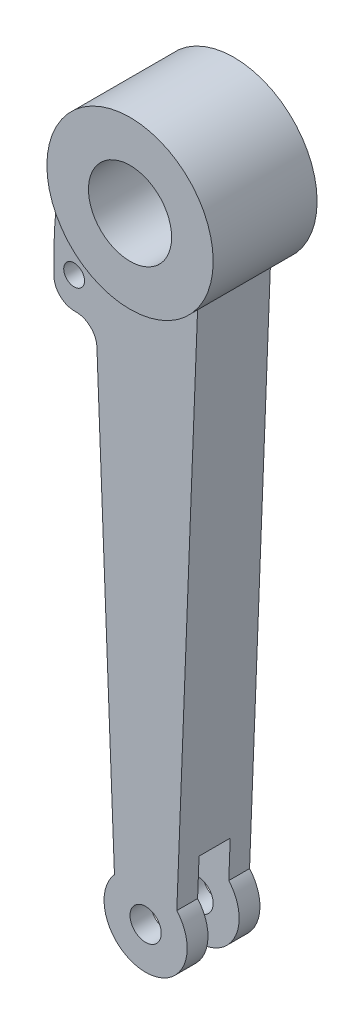
SolidWorks part; units mm, degrees
ref_plane "Front Plane" through (0, 0, 0) normal (0, 0, 1) x (1, 0, 0)
ref_plane "Top Plane" through (0, 0, 0) normal (0, 1, 0) x (1, 0, 0)
ref_plane "Right Plane" through (0, 0, 0) normal (1, 0, 0) x (0, 0, -1)
sketch "Sketch1" plane through (0, 0, 0) normal (0, 0, 1) x (1, 0, 0)
  circle A0 centre (0, 0) radius 40
  circle A1 centre (0, 0) radius 20
  dimension "D1" = 80
  dimension "D2" = 40
extrude "Boss-Extrude1" add sketch "Sketch1" along normal mid plane 50
sketch "Sketch3" plane through (0, 0, 0) normal (0, 0, 1) x (1, 0, 0)
  line L0 (-25, -31.225) -> (-15, -286.7712)
  line L1 (-20, -300) -> (20, -300) construction
  line L2 (15, -286.7712) -> (25, -31.225)
  line L3 (-25, -31.225) -> (0, -31.225) construction
  line L4 (0, -31.225) -> (25, -31.225) construction
  line L5 (0, -31.225) -> (0, 0) construction
  line L6 (-15, -286.7712) -> (15, -286.7712) construction
  circle A0 centre (0, 0) radius 40 construction
  arc A1 (-25, -31.225) -> (25, -31.225) centre (0, 0) ccw
  arc A2 (-15, -286.7712) -> (15, -286.7712) centre (0, -300) ccw
  circle A3 centre (0, -300) radius 7.5
  dimension "D1" = 50
  dimension "D4" = 40
  dimension "D5" = 15
  dimension "D2" = 40
  dimension "D3" = 300
  dimension "D6" = 30
extrude "Boss-Extrude3" add sketch "Sketch3" along normal mid plane 35
sketch "Sketch5" plane through (0, 0, 0) normal (0, 0, 1) x (1, 0, 0)
  circle A0 centre (0, -300) radius 35
  dimension "D1" = 70
extrude "Cut-Extrude1" cut sketch "Sketch5" against normal mid plane 15
sketch "Sketch6" plane through (-26.1818, -1.0245, 0) normal (-0.9992, -0.0391, 0) x (0, 0, 1)
  line L0 (0, 0) -> (0, -267.9024) construction
  line L1 (-7.5, -267.9024) -> (7.5, -267.9024) construction
  line L2 (17.5, -30.2236) -> (17.5, -285.9654) construction
  line L3 (-17.5, -30.2236) -> (17.5, -30.2236)
  line L4 (-17.5, -30.2236) -> (-17.5, -60.2236)
  line L5 (-17.5, -60.2236) -> (17.5, -60.2236)
  line L6 (17.5, -30.2236) -> (17.5, -60.2236)
  line L7 (-17.5, -30.2236) -> (17.5, -60.2236) construction
  line L8 (-17.5, -60.2236) -> (17.5, -30.2236) construction
  line L9 (17.5, -30.2236) -> (-17.5, -30.2236) construction
  line L10 (5, -30.2236) -> (5, -60.2236)
  line L11 (-5, -30.2236) -> (-5, -60.2236)
  line L12 (5, -45.2236) -> (0, -45.2236) construction
  line L13 (0, -45.2236) -> (-5, -45.2236) construction
  point P5 (0, -45.2236)
  line M11 (17.5, -285.9654) -> (17.5, -30.2236)
  line M12 (17.5, -30.2236) -> (-17.5, -30.2236)
  line M13 (-17.5, -30.2236) -> (-17.5, -285.9654)
  dimension "D1" = 30
  dimension "D2" = 10
extrude "Boss-Extrude4" add sketch "Sketch6" along normal blind 20 contours L10 L5 M12 M11 | L11 L5 M12 M13 region at (-24.4135, -46.2135, -11.25) region at (-24.4135, -46.2135, 11.25)
sketch "Sketch7" plane through (0, 0, -17.5) normal (0, 0, -1) x (-1, 0, 0)
  line L0 (44.9847, -32.007) -> (23.8269, -61.202) construction
  circle A0 centre (34.4058, -46.6045) radius 5
  dimension "D1" = 10
extrude "Cut-Extrude2" cut sketch "Sketch7" against normal through all
sketch "Sketch8" plane through (0, 0, -17.5) normal (0, 0, -1) x (-1, 0, 0)
  line L0 (44.9847, -32.007) -> (40, 0)
  line L1 (25, -31.225) -> (44.9847, -32.007)
  line L2 (0, 0) -> (40, 0) construction
  circle A0 centre (0, 0) radius 40 construction
  arc A1 (40, 0) -> (25, -31.225) centre (0, 0) cw
extrude "Boss-Extrude5" add sketch "Sketch8" against normal blind 12.5
mirror "Mirror2" about plane through (0, 0, 0) normal (0, 0, 1) of "Boss-Extrude5"
fillet "Fillet1" radius 250 2 edges at (-44.9847, -32.007, -11.25) (-44.9847, -32.007, 11.25)
fillet "Fillet2" radius 10 2 edges at (-43.8116, -61.9841, -11.25) (-43.8116, -61.9841, 11.25)
fillet "Fillet3" radius 10 2 edges at (-23.8269, -61.202, 11.25) (-23.8269, -61.202, -11.25)
